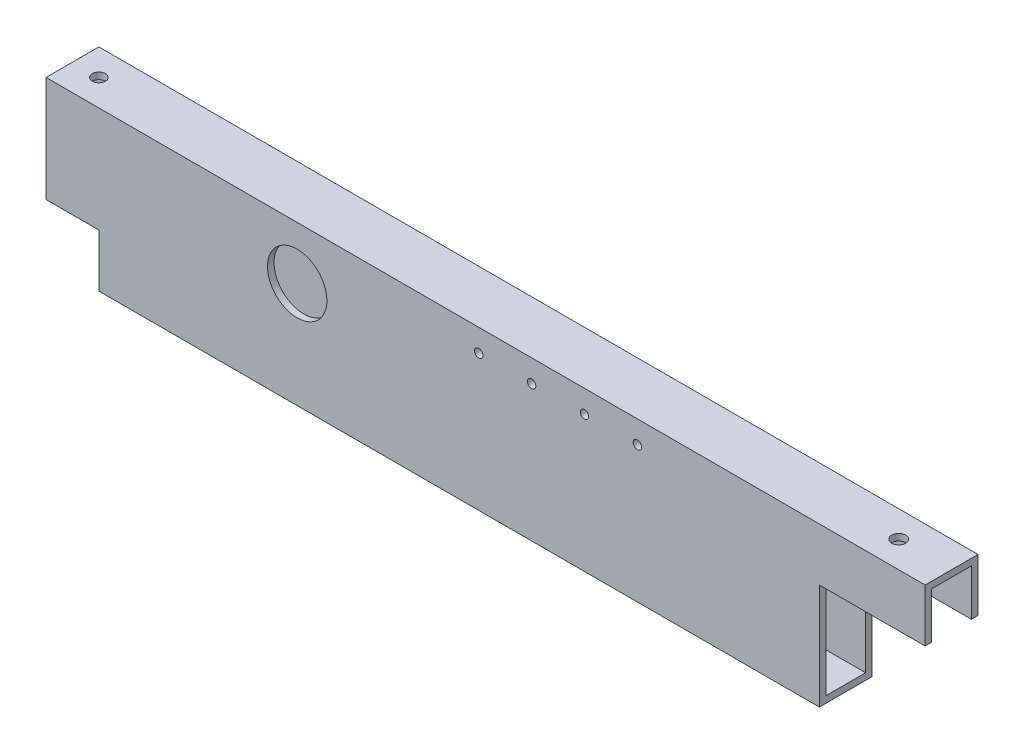
SolidWorks part; units mm, degrees
ref_plane "Front Plane" through (0, 0, 0) normal (0, 0, 1) x (1, 0, 0)
ref_plane "Top Plane" through (0, 0, 0) normal (0, 1, 0) x (1, 0, 0)
ref_plane "Right Plane" through (0, 0, 0) normal (1, 0, 0) x (0, 0, -1)
sketch "Sketch1" plane through (0, 0, 0) normal (0, 0, 1) x (1, 0, 0)
  line L0 (-288.925, -12.7) -> (-263.525, -12.7)
  line L1 (-288.925, 38.1) -> (288.925, 38.1)
  line L2 (-288.925, 38.1) -> (-288.925, -38.1)
  line L3 (-288.925, -38.1) -> (288.925, -38.1)
  line L4 (288.925, 38.1) -> (288.925, -38.1)
  line L5 (-288.925, 38.1) -> (288.925, -38.1) construction
  line L6 (-288.925, -38.1) -> (288.925, 38.1) construction
  line L7 (-288.925, -38.1) -> (-282.575, -38.1) construction
  line L8 (-288.925, -38.1) -> (-288.925, -31.75) construction
  line L9 (-288.925, -31.75) -> (-282.575, -31.75) construction
  line L10 (-282.575, -38.1) -> (-282.575, -31.75) construction
  line L11 (288.925, -38.1) -> (277.3518, -38.1) construction
  line L12 (288.925, -38.1) -> (288.925, -26.5268) construction
  line L13 (288.925, -26.5268) -> (277.3518, -26.5268) construction
  line L14 (277.3518, -38.1) -> (277.3518, -26.5268) construction
  line L15 (-263.525, -12.7) -> (-263.525, -38.1)
  line L16 (263.525, -38.1) -> (263.525, -12.7)
  line L17 (263.525, -12.7) -> (288.925, -12.7)
  point P0 (0, 0)
  dimension "D1" = 577.85
  dimension "D2" = 76.2
  dimension "D3" = 6.35
  dimension "D4" = 25.4
  dimension "D5" = 25.4
extrude "Boss-Extrude1" add sketch "Sketch1" along normal mid plane 25.4 contours L3 L14 L13 L4 L1 L2 L9 L10 region at (0, 0.7668, 0)
hole_wizard "1/4 (0.25) Diameter Hole1" positions "Sketch4" profile "Sketch3" hole size "1/4" standard "ANSI Inch" end condition through all
sketch "Sketch4" plane through (0, 38.1, 0) normal (0, 1, 0) x (1, 0, 0)
  line L0 (-288.925, -12.7) -> (-288.925, 12.7) construction
  line L1 (288.925, -12.7) -> (288.925, 12.7) construction
  point P0 (-276.225, 0)
  point P2 (276.225, 0)
  point P5 (-288.925, 0)
  dimension "D1" = 12.7
  dimension "D2" = 12.7
sketch "Sketch3" plane through (-276.225, 38.1, 0) normal (1, 0, 0) x (0, 0, 1)
  line L0 (0, 0) -> (0, 76.2)
  line L1 (0, 76.2) -> (3.175, 76.2)
  line L2 (3.175, 76.2) -> (3.175, 0)
  line L5 (3.175, 0) -> (0, 0)
  line L11 (0, -6.35) -> (0, 107.95) construction
  dimension "Thru Hole Dia." = 6.35
  dimension "Thru Hole Depth" = 76.2
sketch "Sketch5" plane through (288.925, 0, 0) normal (1, 0, 0) x (0, 0, -1)
  line L27 (9.525, -12.7) -> (9.525, 34.925)
  line L28 (9.525, -34.925) -> (9.525, -12.7)
  line L29 (-9.525, -12.7) -> (-9.525, -34.925)
  line L30 (-9.525, -34.925) -> (9.525, -34.925)
  line L31 (-9.525, 34.925) -> (-9.525, -12.7)
  line L32 (9.525, 34.925) -> (-9.525, 34.925)
  line L33 (9.525, -12.7) -> (9.525, 34.925)
  line L34 (9.525, -34.925) -> (9.525, -12.7)
  line L35 (-9.525, -12.7) -> (-9.525, -34.925)
  line L36 (-9.525, -34.925) -> (9.525, -34.925)
  line L37 (-9.525, 34.925) -> (-9.525, -12.7)
  line L38 (9.525, 34.925) -> (-9.525, 34.925)
  dimension "D1" = 3.175
extrude "Cut-Extrude1" cut sketch "Sketch5" against normal through all
sketch "Sketch8" plane through (0, 0, 12.7) normal (0, 0, 1) x (1, 0, 0)
  line L0 (-288.925, 38.1) -> (288.925, 38.1) construction
  line L1 (-288.925, 38.1) -> (-288.925, -12.7) construction
  line L2 (288.925, 38.1) -> (288.925, -12.7) construction
  circle A0 centre (-168.275, 12.7) radius 14.2875
  circle A1 centre (168.275, 12.7) radius 14.2875
  dimension "D1" = 25.4
  dimension "D2" = 28.575
  dimension "D3" = 120.65
  dimension "D4" = 25.4
  dimension "D5" = 120.65
extrude "Cut-Extrude2" cut sketch "Sketch8" against normal through all
hole_wizard "#10-32 Tapped Hole1" positions "Sketch10" profile "Sketch9" tap size "#10-32" standard "ANSI Inch"
sketch "Sketch10" plane through (0, 0, 12.7) normal (0, 0, 1) x (1, 0, 0)
  line L0 (-288.925, 38.1) -> (-288.925, -12.7) construction
  point P0 (-81.0692, 27.3116)
  point P8 (-55.6692, 27.3116)
  point P9 (-30.2692, 27.3116)
  point P10 (-4.8692, 27.3116)
  dimension "D1" = 207.8558
  dimension "D2" = 4
sketch "Sketch9" plane through (-81.0692, 27.3116, 12.7) normal (1, 0, 0) x (0, -1, 0)
  line L0 (0, 0) -> (0, 14.9293)
  line L1 (0, 14.9293) -> (2.0193, 13.716)
  line L2 (2.0193, 13.716) -> (2.0193, 0)
  line L5 (2.0193, 0) -> (0, 0)
  line L10 (0, 14.9293) -> (-2.0193, 13.716) construction
  line L11 (0, -6.35) -> (0, 107.95) construction
  dimension "Tap Drill Dia." = 4.0386
  dimension "Tap Drill Depth" = 13.716
  dimension "Drill Angle" = 118
cosmetic thread "Hole Thread1" parameters "D1"=3.175, "D2"=4.826
cosmetic thread "Hole Thread2" parameters "D1"=3.175, "D2"=4.826
cosmetic thread "Hole Thread3" parameters "D1"=3.175, "D2"=4.826
cosmetic thread "Hole Thread4" parameters "D1"=3.175, "D2"=4.826
sketch "Sketch11" plane through (0, 0, 12.7) normal (0, 0, 1) x (1, 0, 0)
  line L0 (-263.525, -38.1) -> (263.525, -38.1) construction
  line L1 (288.925, 38.1) -> (133.35, 38.1)
  line L2 (288.925, 38.1) -> (288.925, -38.1)
  line L3 (288.925, -38.1) -> (133.35, -38.1)
  line L4 (133.35, 38.1) -> (133.35, -38.1)
  dimension "D1" = 155.575
extrude "Cut-Extrude3" cut sketch "Sketch11" against normal through all
sketch "Sketch13" plane through (0, 0, 12.7) normal (0, 0, 1) x (1, 0, 0)
  line L1 (133.35, -38.1) -> (82.55, -38.1)
  line L2 (133.35, -38.1) -> (133.35, 12.7)
  line L3 (133.35, 12.7) -> (82.55, 12.7)
  line L4 (82.55, -38.1) -> (82.55, 12.7)
  dimension "D1" = 50.8
  dimension "D2" = 50.8
extrude "Cut-Extrude5" cut sketch "Sketch13" against normal through all
hole_wizard "1/4 Clearance Hole1" positions "Sketch16" profile "Sketch14" hole size "1/4" standard "ANSI Inch" end condition through all
sketch "Sketch16" plane through (0, 38.1, 0) normal (0, 1, 0) x (1, 0, 0)
  line L0 (133.35, 12.7) -> (133.35, -12.7) construction
  point P0 (107.95, 0)
  dimension "D1" = 25.4
sketch "Sketch14" plane through (107.95, 38.1, 0) normal (1, 0, 0) x (0, 0, 1)
  line L0 (0, 0) -> (0, 76.2)
  line L1 (0, 76.2) -> (3.3782, 76.2)
  line L2 (3.3782, 76.2) -> (3.3782, 0)
  line L5 (3.3782, 0) -> (0, 0)
  line L11 (0, -6.35) -> (0, 107.95) construction
  dimension "Thru Hole Dia." = 6.7564
  dimension "Thru Hole Depth" = 76.2
